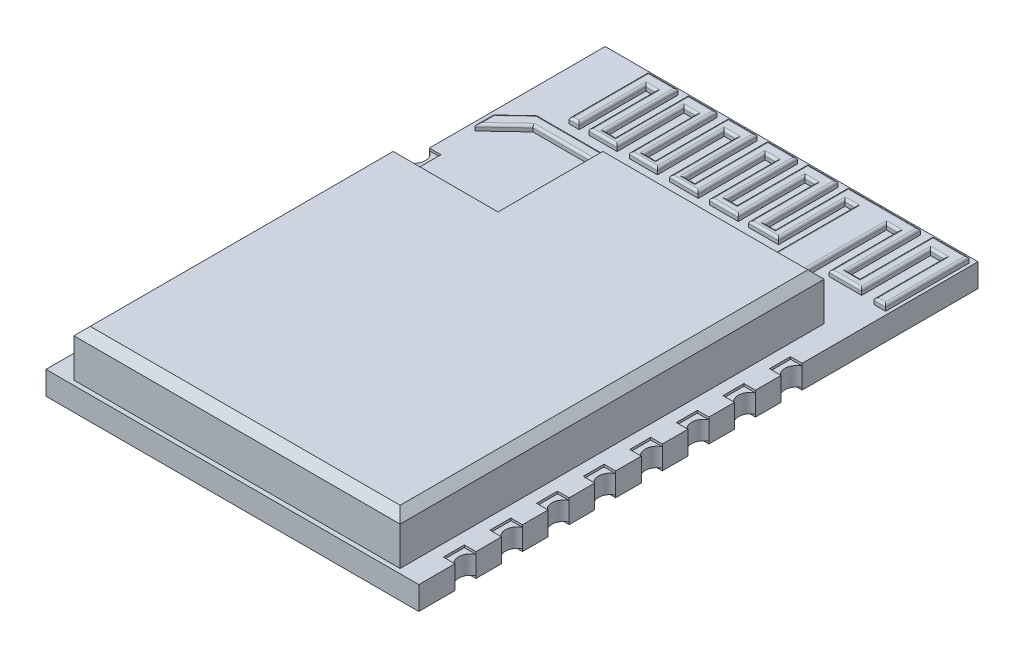
SolidWorks part; units mm, degrees
ref_plane "前基準面" through (0, 0, 0) normal (0, 0, 1) x (1, 0, 0)
ref_plane "上基準面" through (0, 0, 0) normal (0, 1, 0) x (1, 0, 0)
ref_plane "右基準面" through (0, 0, 0) normal (1, 0, 0) x (0, 0, -1)
sketch "草圖1" plane through (0, 0, 0) normal (0, 1, 0) x (1, 0, 0)
  line L5 (-8, 12) -> (8, 12)
  line L6 (-8, 12) -> (-8, -12)
  line L7 (-8, -12) -> (8, -12)
  line L8 (8, 12) -> (8, -12)
  line L9 (-8, 12) -> (8, -12) construction
  line L10 (-8, -12) -> (8, 12) construction
  point P0 (0, 0)
  dimension "D1" = 16
  dimension "24" = 24
extrude "填料-伸長1" add sketch "草圖1" along normal blind 1
sketch "草圖2" plane through (0, 1, 0) normal (0, 1, 0) x (1, 0, 0)
  line L0 (0, 0) -> (0, -5.3119)
  line L1 (-8.003, -9.55) -> (-7.503, -9.55)
  line L2 (-8.003, -9.55) -> (-8.003, -10.45)
  line L3 (-8.003, -10.45) -> (-7.503, -10.45)
  line L4 (-7.503, -9.55) -> (-7.503, -10.45)
  line L5 (8.003, -10.45) -> (7.503, -10.45)
  line L6 (7.503, -9.55) -> (7.503, -10.45)
  line L7 (8.003, -9.55) -> (7.503, -9.55)
  line L8 (8.003, -9.55) -> (8.003, -10.45)
  line L9 (-8.003, -7.55) -> (-8.003, -8.45)
  line L10 (-8.003, -7.55) -> (-7.503, -7.55)
  line L11 (-7.503, -7.55) -> (-7.503, -8.45)
  line L12 (-8.003, -8.45) -> (-7.503, -8.45)
  line L13 (-8.003, -5.55) -> (-8.003, -6.45)
  line L14 (-8.003, -5.55) -> (-7.503, -5.55)
  line L15 (-7.503, -5.55) -> (-7.503, -6.45)
  line L16 (-8.003, -6.45) -> (-7.503, -6.45)
  line L17 (-8.003, -3.55) -> (-8.003, -4.45)
  line L18 (-8.003, -3.55) -> (-7.503, -3.55)
  line L19 (-7.503, -3.55) -> (-7.503, -4.45)
  line L20 (-8.003, -4.45) -> (-7.503, -4.45)
  line L21 (-8.003, -1.55) -> (-8.003, -2.45)
  line L22 (-8.003, -1.55) -> (-7.503, -1.55)
  line L23 (-7.503, -1.55) -> (-7.503, -2.45)
  line L24 (-8.003, -2.45) -> (-7.503, -2.45)
  line L25 (-8.003, 0.45) -> (-8.003, -0.45)
  line L26 (-8.003, 0.45) -> (-7.503, 0.45)
  line L27 (-7.503, 0.45) -> (-7.503, -0.45)
  line L28 (-8.003, -0.45) -> (-7.503, -0.45)
  line L29 (-8.003, 2.45) -> (-8.003, 1.55)
  line L30 (-8.003, 2.45) -> (-7.503, 2.45)
  line L31 (-7.503, 2.45) -> (-7.503, 1.55)
  line L32 (-8.003, 1.55) -> (-7.503, 1.55)
  line L33 (-8.003, 4.45) -> (-8.003, 3.55)
  line L34 (-8.003, 4.45) -> (-7.503, 4.45)
  line L35 (-7.503, 4.45) -> (-7.503, 3.55)
  line L36 (-8.003, 3.55) -> (-7.503, 3.55)
  line L42 (8.003, -8.45) -> (7.503, -8.45)
  line L43 (7.503, -7.55) -> (7.503, -8.45)
  line L44 (8.003, -7.55) -> (7.503, -7.55)
  line L45 (8.003, -7.55) -> (8.003, -8.45)
  line L46 (8.003, -6.45) -> (7.503, -6.45)
  line L47 (7.503, -5.55) -> (7.503, -6.45)
  line L48 (8.003, -5.55) -> (7.503, -5.55)
  line L49 (8.003, -5.55) -> (8.003, -6.45)
  line L50 (8.003, -4.45) -> (7.503, -4.45)
  line L51 (7.503, -3.55) -> (7.503, -4.45)
  line L52 (8.003, -3.55) -> (7.503, -3.55)
  line L53 (8.003, -3.55) -> (8.003, -4.45)
  line L54 (8.003, -2.45) -> (7.503, -2.45)
  line L55 (7.503, -1.55) -> (7.503, -2.45)
  line L56 (8.003, -1.55) -> (7.503, -1.55)
  line L57 (8.003, -1.55) -> (8.003, -2.45)
  line L58 (8.003, -0.45) -> (7.503, -0.45)
  line L59 (7.503, 0.45) -> (7.503, -0.45)
  line L60 (8.003, 0.45) -> (7.503, 0.45)
  line L61 (8.003, 0.45) -> (8.003, -0.45)
  line L62 (8.003, 1.55) -> (7.503, 1.55)
  line L63 (7.503, 2.45) -> (7.503, 1.55)
  line L64 (8.003, 2.45) -> (7.503, 2.45)
  line L65 (8.003, 2.45) -> (8.003, 1.55)
  line L66 (8.003, 3.55) -> (7.503, 3.55)
  line L67 (7.503, 4.45) -> (7.503, 3.55)
  line L68 (8.003, 4.45) -> (7.503, 4.45)
  line L69 (8.003, 4.45) -> (8.003, 3.55)
  point P4 (-8.003, -10)
  line M6 (8, -12) -> (8, 12)
  line M8 (-8, 12) -> (-8, -12)
  dimension "D1" = 2
  dimension "D2" = 8
  dimension "D3" = 8
extrude "除料-伸長1" cut sketch "草圖2" against normal blind 0.1 contours L32 L31 L30 M8 | L28 L27 L26 M8 | L24 L23 L22 M8 | L20 L19 L18 M8 | L16 L15 L14 M8 | L12 L11 L10 M8 | L4 L1 L3 M8 | L7 L6 L5 M6 | L44 L43 L42 M6 | L48 L47 L46 M6 | L52 L51 L50 M6 | L56 L55 L54 M6 | L60 L59 L58 M6 | L68 L67 L66 M6 | L64 L63 L62 M6 | L35 L36 L33 L34 region at (-7.7515, 1, -2) region at (-7.7515, 1, 0) region at (-7.7515, 1, 2) region at (-7.7515, 1, 4) region at (-7.7515, 1, 6) region at (-7.7515, 1, 8) region at (-7.7515, 1, 10) region at (7.7515, 1, -4) region at (7.7515, 1, -2) region at (7.7515, 1, 0) region at (7.7515, 1, 2) region at (7.7515, 1, 4) region at (7.7515, 1, 6) region at (7.7515, 1, 8) region at (7.7515, 1, 10)
sketch "草圖3" plane through (0, 0, 0) normal (0, -1, 0) x (1, 0, 0)
  line L0 (7, 7.55) -> (7, 8.45)
  line L1 (8, 12) -> (8, -12) construction
  line L6 (7, 9.55) -> (8, 9.55)
  line L7 (7, 9.55) -> (7, 10.45)
  line L8 (7, 10.45) -> (8, 10.45)
  line L9 (8, 9.55) -> (8, 10.45)
  line L10 (-8, 12) -> (8, 12) construction
  line L11 (7, 7.55) -> (8, 7.55)
  line L12 (8, 7.55) -> (8, 8.45)
  line L13 (7, 8.45) -> (8, 8.45)
  line L14 (7, 5.55) -> (7, 6.45)
  line L15 (7, 5.55) -> (8, 5.55)
  line L16 (8, 5.55) -> (8, 6.45)
  line L17 (7, 6.45) -> (8, 6.45)
  line L18 (7, 3.55) -> (7, 4.45)
  line L19 (7, 3.55) -> (8, 3.55)
  line L20 (8, 3.55) -> (8, 4.45)
  line L21 (7, 4.45) -> (8, 4.45)
  line L22 (7, 1.55) -> (7, 2.45)
  line L23 (7, 1.55) -> (8, 1.55)
  line L24 (8, 1.55) -> (8, 2.45)
  line L25 (7, 2.45) -> (8, 2.45)
  line L26 (7, -0.45) -> (7, 0.45)
  line L27 (7, -0.45) -> (8, -0.45)
  line L28 (8, -0.45) -> (8, 0.45)
  line L29 (7, 0.45) -> (8, 0.45)
  line L30 (7, -2.45) -> (7, -1.55)
  line L31 (7, -2.45) -> (8, -2.45)
  line L32 (8, -2.45) -> (8, -1.55)
  line L33 (7, -1.55) -> (8, -1.55)
  line L34 (7, -4.45) -> (7, -3.55)
  line L35 (7, -4.45) -> (8, -4.45)
  line L36 (8, -4.45) -> (8, -3.55)
  line L37 (7, -3.55) -> (8, -3.55)
  line L38 (0, 0) -> (0, -2.1829)
  line L39 (-7, 10.45) -> (-8, 10.45)
  line L40 (-8, 9.55) -> (-8, 10.45)
  line L41 (-7, 9.55) -> (-8, 9.55)
  line L42 (-7, 9.55) -> (-7, 10.45)
  line L43 (-7, -4.45) -> (-8, -4.45)
  line L44 (-8, -4.45) -> (-8, -3.55)
  line L45 (-7, -3.55) -> (-8, -3.55)
  line L46 (-7, -4.45) -> (-7, -3.55)
  line L47 (-7, -2.45) -> (-8, -2.45)
  line L48 (-8, -2.45) -> (-8, -1.55)
  line L49 (-7, -1.55) -> (-8, -1.55)
  line L50 (-7, -2.45) -> (-7, -1.55)
  line L51 (-7, -0.45) -> (-8, -0.45)
  line L52 (-8, -0.45) -> (-8, 0.45)
  line L53 (-7, 0.45) -> (-8, 0.45)
  line L54 (-7, -0.45) -> (-7, 0.45)
  line L55 (-7, 1.55) -> (-8, 1.55)
  line L56 (-8, 1.55) -> (-8, 2.45)
  line L57 (-7, 2.45) -> (-8, 2.45)
  line L58 (-7, 1.55) -> (-7, 2.45)
  line L59 (-7, 3.55) -> (-8, 3.55)
  line L60 (-8, 3.55) -> (-8, 4.45)
  line L61 (-7, 4.45) -> (-8, 4.45)
  line L62 (-7, 3.55) -> (-7, 4.45)
  line L63 (-7, 5.55) -> (-8, 5.55)
  line L64 (-8, 5.55) -> (-8, 6.45)
  line L65 (-7, 6.45) -> (-8, 6.45)
  line L66 (-7, 5.55) -> (-7, 6.45)
  line L67 (-7, 7.55) -> (-8, 7.55)
  line L68 (-8, 7.55) -> (-8, 8.45)
  line L69 (-7, 8.45) -> (-8, 8.45)
  line L70 (-7, 7.55) -> (-7, 8.45)
  point P8 (8, 10)
  dimension "D1" = 2
  dimension "D2" = 0.9
  dimension "D3" = 8
extrude "除料-伸長2" cut sketch "草圖3" against normal blind 0.1 contours L67 L70 L69 L9 | L63 L66 L65 L9 | L59 L62 L61 L9 | L51 L54 L53 L9 | L47 L50 L49 L9 | L43 L46 L45 L9 | L33 L30 L31 L7 | L29 L26 L27 L7 | L25 L22 L23 L7 | L21 L18 L19 L7 | L13 L0 L11 L7 | L8 L7 L6 | L41 L40 L39 L42 | L58 L57 L56 L55 | L36 L37 L34 L35 | L17 L16 L15 L14 region at (7.5, 0, 8) region at (7.5, 0, 10) region at (7.5, 0, 4) region at (7.5, 0, 2) region at (7.5, 0, 0) region at (7.5, 0, -2) region at (-7.5, 0, -4) region at (-7.5, 0, -2) region at (-7.5, 0, 0) region at (-7.5, 0, 4) region at (-7.5, 0, 6) region at (-7.5, 0, 8)
sketch "草圖8" plane through (0, 1, 0) normal (0, 1, 0) x (1, 0, 0)
  line L0 (-8, -12) -> (8, -12) construction
  line L1 (-1, 0.6) -> (3.7, 0.6)
  line L2 (-1, 0.6) -> (-1, -4.1)
  line L3 (-1, -4.1) -> (3.7, -4.1)
  line L4 (3.7, 0.6) -> (3.7, -4.1)
  line L5 (-1, 0.6) -> (3.7, -4.1) construction
  line L6 (-1, -4.1) -> (3.7, 0.6) construction
  line L7 (-8, -2.45) -> (-8, -3.55) construction
  point P0 (1.35, -1.75)
  dimension "D1" = 7.9
  dimension "D2" = 7
  dimension "D3" = 4.7
  dimension "D4" = 4.7
extrude "除料-伸長3" cut sketch "草圖8" against normal blind 0.1
sketch "草圖12" plane through (0, 0.9, 0) normal (0, 1, 0) x (1, 0, 0)
  line L0 (-1, 0.6) -> (-1, -4.1) construction
  line L1 (-1, -4.1) -> (3.7, -4.1) construction
  circle A1 centre (-0.51, -3.65) radius 0.2
  circle A2 centre (0.42, -3.65) radius 0.2
  circle A3 centre (1.35, -3.65) radius 0.2
  circle A4 centre (2.28, -3.65) radius 0.2
  circle A5 centre (3.21, -3.65) radius 0.2
  circle A6 centre (-0.51, -2.72) radius 0.2
  circle A7 centre (0.42, -2.72) radius 0.2
  circle A8 centre (1.35, -2.72) radius 0.2
  circle A9 centre (2.28, -2.72) radius 0.2
  circle A10 centre (3.21, -2.72) radius 0.2
  circle A11 centre (-0.51, -1.79) radius 0.2
  circle A12 centre (0.42, -1.79) radius 0.2
  circle A13 centre (1.35, -1.79) radius 0.2
  circle A14 centre (2.28, -1.79) radius 0.2
  circle A15 centre (3.21, -1.79) radius 0.2
  circle A16 centre (-0.51, -0.86) radius 0.2
  circle A17 centre (0.42, -0.86) radius 0.2
  circle A18 centre (1.35, -0.86) radius 0.2
  circle A19 centre (2.28, -0.86) radius 0.2
  circle A20 centre (3.21, -0.86) radius 0.2
  circle A21 centre (-0.51, 0.07) radius 0.2
  circle A22 centre (0.42, 0.07) radius 0.2
  circle A23 centre (1.35, 0.07) radius 0.2
  circle A24 centre (2.28, 0.07) radius 0.2
  circle A25 centre (3.21, 0.07) radius 0.2
  dimension "D1" = 0.49
  dimension "D2" = 0.45
  dimension "D3" = 5
  dimension "D4" = 5
extrude "除料-伸長4" cut sketch "草圖12" against normal blind 0.1
sketch "草圖13" plane through (0, 1, 0) normal (0, 1, 0) x (1, 0, 0)
  line L5 (-1, 0.6) -> (3.7, 0.6)
  line L6 (-1, 0.6) -> (-1, -4.1)
  line L7 (-1, -4.1) -> (3.7, -4.1)
  line L8 (3.7, 0.6) -> (3.7, -4.1)
extrude "填料-伸長2" add sketch "草圖13" against normal blind 0.5
sketch "草圖15" plane through (0, 0, 0) normal (0, -1, 0) x (1, 0, 0)
  line L0 (-8, 12) -> (8, 12) construction
  line L1 (1, -0.6) -> (-3.7, -0.6)
  line L2 (1, -0.6) -> (1, 4.1)
  line L3 (1, 4.1) -> (-3.7, 4.1)
  line L4 (-3.7, -0.6) -> (-3.7, 4.1)
  line L5 (1, -0.6) -> (-3.7, 4.1) construction
  line L6 (1, 4.1) -> (-3.7, -0.6) construction
  line L7 (8, 1.55) -> (8, 0.45) construction
  point P0 (-1.35, 1.75)
  point P9 (8, 1)
  dimension "D1" = 7.9
  dimension "D2" = 7
  dimension "D3" = 4.7
  dimension "D4" = 4.7
extrude "除料-伸長5" cut sketch "草圖15" against normal blind 0.1
sketch "草圖16" plane through (0, 0, 0) normal (0, -1, 0) x (1, 0, 0)
  line L0 (1, 4.1) -> (-3.7, 4.1) construction
  line L1 (1, -0.6) -> (1, 4.1) construction
  circle A0 centre (0.51, 3.61) radius 0.2
  circle A1 centre (-0.42, 3.61) radius 0.2
  circle A2 centre (-1.35, 3.61) radius 0.2
  circle A3 centre (-2.28, 3.61) radius 0.2
  circle A4 centre (-3.21, 3.61) radius 0.2
  circle A5 centre (-3.21, 2.68) radius 0.2
  circle A6 centre (-2.28, 2.68) radius 0.2
  circle A7 centre (-1.35, 2.68) radius 0.2
  circle A8 centre (-0.42, 2.68) radius 0.2
  circle A9 centre (0.51, 2.68) radius 0.2
  circle A10 centre (-3.21, 1.75) radius 0.2
  circle A11 centre (-2.28, 1.75) radius 0.2
  circle A12 centre (-1.35, 1.75) radius 0.2
  circle A13 centre (-0.42, 1.75) radius 0.2
  circle A14 centre (0.51, 1.75) radius 0.2
  circle A15 centre (-3.21, 0.82) radius 0.2
  circle A16 centre (-2.28, 0.82) radius 0.2
  circle A17 centre (-1.35, 0.82) radius 0.2
  circle A18 centre (-0.42, 0.82) radius 0.2
  circle A19 centre (0.51, 0.82) radius 0.2
  circle A20 centre (-3.21, -0.11) radius 0.2
  circle A21 centre (-2.28, -0.11) radius 0.2
  circle A22 centre (-1.35, -0.11) radius 0.2
  circle A23 centre (-0.42, -0.11) radius 0.2
  circle A24 centre (0.51, -0.11) radius 0.2
  dimension "D1" = 0.49
  dimension "D2" = 0.49
  dimension "D3" = 5
  dimension "D4" = 5
extrude "除料-伸長6" cut sketch "草圖16" against normal blind 0.25
sketch "草圖17" plane through (0, 1, 0) normal (0, 1, 0) x (1, 0, 0)
  line L0 (-8, -12) -> (8, -12) construction
  line L5 (-2.5, 6.4) -> (7, 6.4)
  line L6 (-7, 1.4) -> (-7, -10.8)
  line L7 (-7, -10.8) -> (7, -10.8)
  line L8 (7, 6.4) -> (7, -10.8)
  line L9 (-8, 12) -> (-8, 4.45) construction
  line L10 (8, 4.45) -> (8, 12) construction
  line L16 (-2.5, 6.4) -> (-2.5, 1.9)
  line L17 (-2.5, 1.9) -> (-7, 1.9)
  line L18 (-7, 1.9) -> (-7, 1.4)
  dimension "D1" = 1.2
  dimension "D2" = 1
  dimension "D3" = 1
extrude "填料-伸長4" add sketch "草圖17" along normal blind 2
sketch "草圖18" plane through (0, 1, 0) normal (0, 1, 0) x (1, 0, 0)
  line L1 (-8, 4.45) -> (-8, 3.55)
  line L3 (-8, 2.45) -> (-8, 1.55)
  line L4 (-8, 0.45) -> (-8, -0.45)
  line L5 (-8, -1.55) -> (-8, -2.45)
  line L6 (-8, -3.55) -> (-8, -4.45)
  line L7 (-8, -5.55) -> (-8, -6.45)
  line L8 (-8, -7.55) -> (-8, -8.45)
  line L9 (-8, -9.55) -> (-8, -10.45)
  line L12 (8, 4.45) -> (8, 3.55)
  line L13 (8, 2.45) -> (8, 1.55)
  line L14 (8, 0.45) -> (8, -0.45)
  line L15 (8, -1.55) -> (8, -2.45)
  line L16 (8, -3.55) -> (8, -4.45)
  line L17 (8, -5.55) -> (8, -6.45)
  line L18 (8, -7.55) -> (8, -8.45)
  line L19 (8, -9.55) -> (8, -10.45)
  arc A0 (-8, 4.45) -> (-8, 3.55) centre (-8.2179, 4) cw
  arc A1 (-8, 2.45) -> (-8, 1.55) centre (-8.2179, 2) cw
  arc A2 (-8, 0.45) -> (-8, -0.45) centre (-8.2179, 0) cw
  arc A3 (-8, -1.55) -> (-8, -2.45) centre (-8.2179, -2) cw
  arc A4 (-8, -3.55) -> (-8, -4.45) centre (-8.2179, -4) cw
  arc A5 (-8, -5.55) -> (-8, -6.45) centre (-8.2179, -6) cw
  arc A6 (-8, -7.55) -> (-8, -8.45) centre (-8.2179, -8) cw
  arc A7 (-8, -9.55) -> (-8, -10.45) centre (-8.2179, -10) cw
  arc A8 (8, 4.45) -> (8, 3.55) centre (8.2179, 4) ccw
  arc A9 (8, 2.45) -> (8, 1.55) centre (8.2179, 2) ccw
  arc A10 (8, 0.45) -> (8, -0.45) centre (8.2179, 0) ccw
  arc A11 (8, -1.55) -> (8, -2.45) centre (8.2179, -2) ccw
  arc A12 (8, -3.55) -> (8, -4.45) centre (8.2179, -4) ccw
  arc A13 (8, -5.55) -> (8, -6.45) centre (8.2179, -6) ccw
  arc A14 (8, -7.55) -> (8, -8.45) centre (8.2179, -8) ccw
  arc A15 (8, -9.55) -> (8, -10.45) centre (8.2179, -10) ccw
  dimension "D1" = 8
extrude "除料-伸長7" cut sketch "草圖18" against normal blind 2
sketch "草圖19" plane through (0, 1, 0) normal (0, 1, 0) x (1, 0, 0)
  line L0 (-144.5969, 121.1687) -> (-19.9302, 121.1687) construction
  line L1 (-7, -10.8) -> (-7, -11.8025)
  line L2 (-7, -11.8025) -> (7, -11.8025)
  line L3 (7, -10.8) -> (7, -11.8025)
  line L4 (7, -10.8) -> (7, -11.8025)
  line L5 (-7, -10.8) -> (7, -10.8)
extrude "填料-伸長5" add sketch "草圖19" along normal up to surface (2 mm away) contours L5 L1 L2 L3 region at (0, 1, 11.3012) up to face at (-0.8333, 3, 0.8333)
sketch "草圖20" plane through (0, 1, 0) normal (0, 1, 0) x (1, 0, 0)
  line L0 (23.4441, 125.3473) -> (148.1108, 125.3473) construction
  line L1 (2.7746, 7.2994) -> (2.7746, 6.4)
  line L3 (7, 6.4) -> (-2.5, 6.4) construction
  line L4 (2.7746, 7.2994) -> (4.8557, 7.2994)
  line L5 (4.8557, 7.2994) -> (4.8557, 11.2142)
  line L6 (4.8557, 11.2142) -> (5.3615, 11.2142)
  line L7 (5.3615, 11.2142) -> (5.3615, 8.253)
  line L8 (5.3615, 8.253) -> (6.7537, 8.253)
  line L9 (6.7537, 8.253) -> (6.7537, 11.2142)
  line L10 (6.7537, 11.2142) -> (7.3504, 11.2142)
  line L11 (7.3504, 11.2142) -> (7.3504, 8.1756)
  line L12 (7.3504, 8.1756) -> (7.8586, 8.1756)
  line L13 (7.8586, 8.1756) -> (7.8586, 11.7556)
  line L14 (7.8586, 11.7556) -> (6.3117, 11.7556)
  line L15 (6.3117, 11.7556) -> (6.3117, 8.6286)
  line L16 (6.3117, 8.6286) -> (5.8587, 8.6286)
  line L17 (5.8587, 8.6286) -> (5.7703, 8.6286)
  line L18 (5.7703, 8.6286) -> (5.7703, 11.7556)
  line L19 (5.7703, 11.7556) -> (2.6765, 11.7556)
  line L20 (2.6765, 11.7556) -> (2.6765, 8.6286)
  line L21 (2.6765, 8.6286) -> (2.2345, 8.6286)
  line L22 (2.2345, 8.6286) -> (2.2345, 11.7556)
  line L23 (2.2345, 11.7556) -> (0.9417, 11.7556)
  line L24 (0.9417, 11.7556) -> (0.9417, 8.7281)
  line L25 (0.9417, 8.7281) -> (0.4887, 8.7281)
  line L26 (0.4887, 8.7281) -> (0.4887, 11.7556)
  line L27 (0.4887, 11.7556) -> (-0.782, 11.7556)
  line L28 (-0.782, 11.7556) -> (-0.782, 8.6286)
  line L29 (-0.782, 8.6286) -> (-1.235, 8.6286)
  line L30 (-1.235, 8.6286) -> (-1.235, 11.7556)
  line L31 (-1.235, 11.7556) -> (-2.4725, 11.7556)
  line L32 (-2.4725, 11.7556) -> (-2.4725, 8.6286)
  line L33 (-2.4725, 8.6286) -> (-2.9587, 8.6286)
  line L34 (-2.9587, 8.6286) -> (-2.9587, 11.7556)
  line L35 (-2.9587, 11.7556) -> (-4.1852, 11.7556)
  line L36 (-4.1852, 11.7556) -> (-4.1852, 8.6286)
  line L37 (-4.1852, 8.6286) -> (-4.6323, 8.6286)
  line L38 (-4.6323, 8.6286) -> (-4.6323, 11.7556)
  line L39 (-4.6323, 11.7556) -> (-5.9045, 11.7556)
  line L40 (-5.9045, 11.7556) -> (-5.9045, 8.3512)
  line L41 (-5.9045, 8.3512) -> (-5.4695, 8.3512)
  line L42 (-5.4695, 8.3512) -> (-5.4695, 11.2142)
  line L43 (-5.4695, 11.2142) -> (-5.0563, 11.2142)
  line L44 (-5.0563, 11.2142) -> (-5.0563, 8.3512)
  line L45 (-5.0563, 8.3512) -> (-3.8385, 8.3512)
  line L46 (-3.8385, 8.3512) -> (-3.8385, 11.2142)
  line L47 (-3.8385, 11.2142) -> (-3.3166, 11.2142)
  line L48 (-3.3166, 11.2142) -> (-3.3166, 8.3512)
  line L49 (-3.3166, 8.3512) -> (-2.1096, 8.3512)
  line L50 (-2.1096, 8.3512) -> (-2.1096, 11.2142)
  line L51 (-2.1096, 11.2142) -> (-1.5877, 11.2142)
  line L52 (-1.5877, 11.2142) -> (-1.5877, 8.3512)
  line L53 (-1.5877, 8.3512) -> (-0.3589, 8.3512)
  line L54 (-0.3589, 8.3512) -> (-0.3589, 11.2142)
  line L55 (-0.3589, 11.2142) -> (0.1195, 11.2142)
  line L56 (0.1195, 11.2142) -> (0.1195, 8.3512)
  line L57 (0.1195, 8.3512) -> (1.3591, 8.3512)
  line L58 (1.3591, 8.3512) -> (1.3591, 11.2142)
  line L59 (1.3591, 11.2142) -> (1.8049, 11.2142)
  line L60 (1.8049, 11.2142) -> (1.8049, 8.3512)
  line L61 (1.8049, 8.3512) -> (3.088, 8.3512)
  line L62 (3.088, 8.3512) -> (3.088, 11.2142)
  line L63 (3.088, 11.2142) -> (3.523, 11.2142)
  line L64 (3.523, 11.2142) -> (3.523, 7.764)
  line L65 (3.523, 7.764) -> (-6.6874, 7.764)
  line L66 (-6.6874, 7.764) -> (-7.6552, 6.8497)
  line L67 (-7.6552, 6.8497) -> (-7.6552, 6.1428)
  line L68 (-6.3743, 7.2733) -> (2.2333, 7.2733)
  line L69 (2.2333, 7.2733) -> (2.25, 6.4)
  line L70 (-6.3743, 7.2733) -> (-7.5709, 6.1428)
  line L71 (7, 6.4) -> (-2.5, 6.4) construction
  line L72 (2.25, 6.4) -> (2.7746, 6.4)
  line L73 (-7.6552, 6.1428) -> (-7.6552, 6.0749)
  line L75 (-7.5709, 6.1428) -> (-7.6552, 6.0632)
  line L76 (-7.6552, 6.0632) -> (-7.6552, 6.0749)
ref_plane "平面1" through (8, 1, -4.45) normal (0, 0, -1) x (-1, 0, 0)
extrude "填料-伸長7" add sketch "草圖20" along normal blind 0.25 contours L65 L66 L67 L73 L76 L75 L70 L68 L69 L72 L1 L4 L5 L6 L7 L8 L9 L10 L11 L12 L13 L14 L15 L16 L17 L18 L19 L20 L21 L22 L23 L24 L25 L26 L27 L28 L29 L30 L31 L32 L33 L34 L35 L36 L37 L38 L39 L40 L41 L42 L43 L44 L45 L46 L47 L48 L49 L50 L51 L52 L53 L54 L55 L56 L57 L58 L59 L60 L61 L62 L63 L64
fillet "圓角2" radius 0.1 70 edges at (2.7746, 1.125, -6.4) (2.25, 1.125, -6.4) (3.3055, 1.25, -11.2142) (3.088, 1.25, -9.7827) (2.4465, 1.25, -8.3512) (1.8049, 1.25, -9.7827) (1.582, 1.25, -11.2142) (1.3591, 1.25, -9.7827) (0.7393, 1.25, -8.3512) (0.1195, 1.25, -9.7827) (-0.1197, 1.25, -11.2142) (-0.3589, 1.25, -9.7827) (-0.9733, 1.25, -8.3512) (-1.5877, 1.25, -9.7827) (-1.8486, 1.25, -11.2142) (-2.1096, 1.25, -9.7827) (-2.7131, 1.25, -8.3512) (-3.3166, 1.25, -9.7827) (-3.5775, 1.25, -11.2142) (-3.8385, 1.25, -9.7827) (-4.4474, 1.25, -8.3512) (-5.0563, 1.25, -9.7827) (-5.2629, 1.25, -11.2142) (-5.4695, 1.25, -9.7827) (-5.687, 1.25, -8.3512) (-5.9045, 1.25, -10.0534) (-5.2684, 1.25, -11.7556) (-4.6323, 1.25, -10.1921) (-4.4087, 1.25, -8.6286) (-4.1852, 1.25, -10.1921) (-3.572, 1.25, -11.7556) (-2.9587, 1.25, -10.1921) (-2.7156, 1.25, -8.6286) (-2.4725, 1.25, -10.1921) (-1.8538, 1.25, -11.7556) (-1.235, 1.25, -10.1921) (-1.0085, 1.25, -8.6286) (-0.782, 1.25, -10.1921) (-0.1466, 1.25, -11.7556) (0.4887, 1.25, -10.2418) (0.7152, 1.25, -8.7281) (0.9417, 1.25, -10.2418) (1.5881, 1.25, -11.7556) (2.2345, 1.25, -10.1921) (2.4555, 1.25, -8.6286) (2.6765, 1.25, -10.1921) (4.2234, 1.25, -11.7556) (5.7703, 1.25, -10.1921) (6.041, 1.25, -8.6286) (6.3117, 1.25, -10.1921) (7.0852, 1.25, -11.7556) (7.8586, 1.25, -9.9656) (7.6045, 1.25, -8.1756) (7.3504, 1.25, -9.6949) (7.052, 1.25, -11.2142) (6.7537, 1.25, -9.7336) (6.0576, 1.25, -8.253) (5.3615, 1.25, -9.7336) (5.1086, 1.25, -11.2142) (4.8557, 1.25, -9.2568) (3.8151, 1.25, -7.2994) (2.7746, 1.25, -6.8497) (2.5123, 1.25, -6.4) (2.2417, 1.25, -6.8367) (-2.0705, 1.25, -7.2733) (-7.0147, 1.25, -6.6683) (-7.6552, 1.25, -6.4565) (-7.1713, 1.25, -7.3069) (-1.5822, 1.25, -7.764) (3.523, 1.25, -9.4891)
chamfer "導角1" distance 0.35 angle 45 6 edges at (0, 3, 11.8025) (-7, 3, 4.9512) (-4.75, 3, -1.9) (-2.5, 3, -4.15) (2.25, 3, -6.4) (7, 3, 2.7012)
